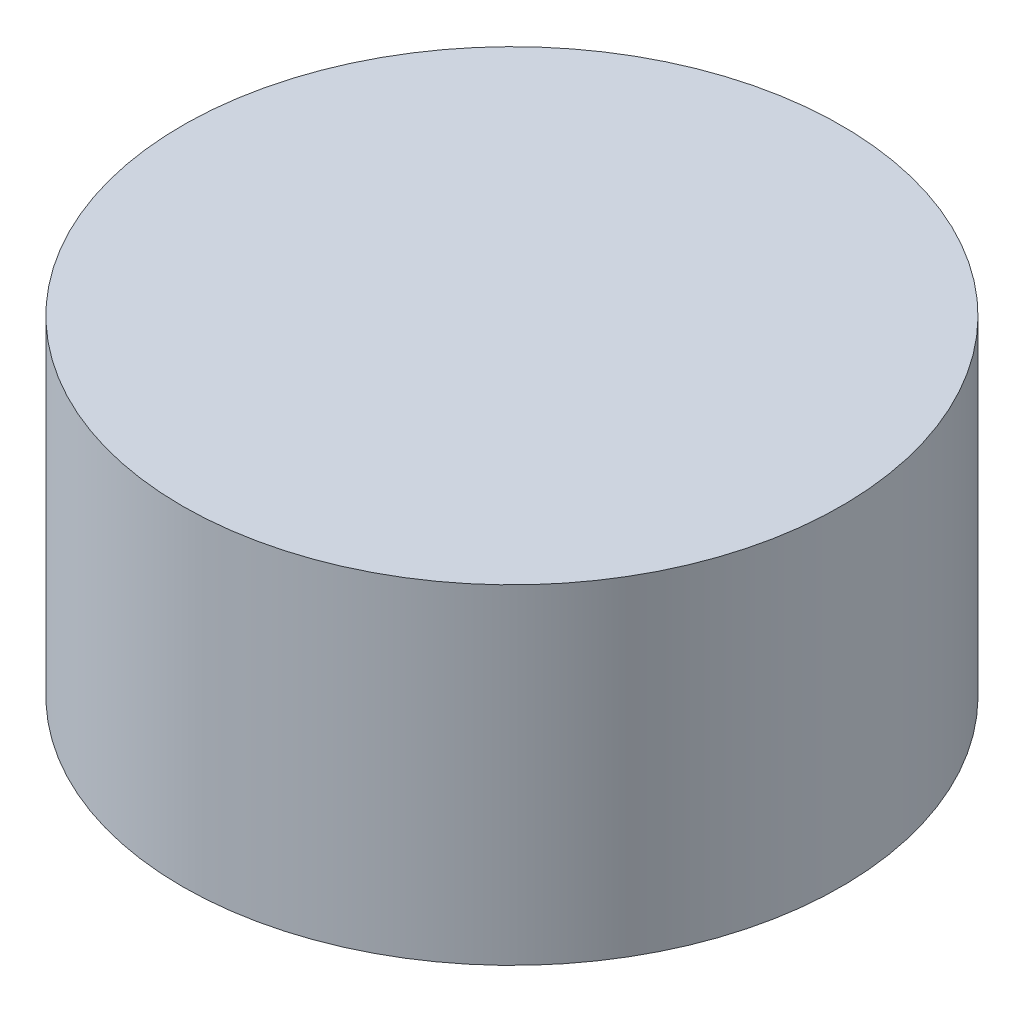
SolidWorks part; units mm, degrees
ref_plane "Front Plane" through (0, 0, 0) normal (0, 0, 1) x (1, 0, 0)
ref_plane "Top Plane" through (0, 0, 0) normal (0, 1, 0) x (1, 0, 0)
ref_plane "Right Plane" through (0, 0, 0) normal (1, 0, 0) x (0, 0, -1)
sketch "Sketch1" plane through (0, 0, 0) normal (0, 1, 0) x (1, 0, 0)
  circle A0 centre (0, 0) radius 50
extrude "Boss-Extrude1" add sketch "Sketch1" along normal blind 50 contours A0
ref_axis "Axis1" through (0, 50, 0) along (0, -1, 0)
